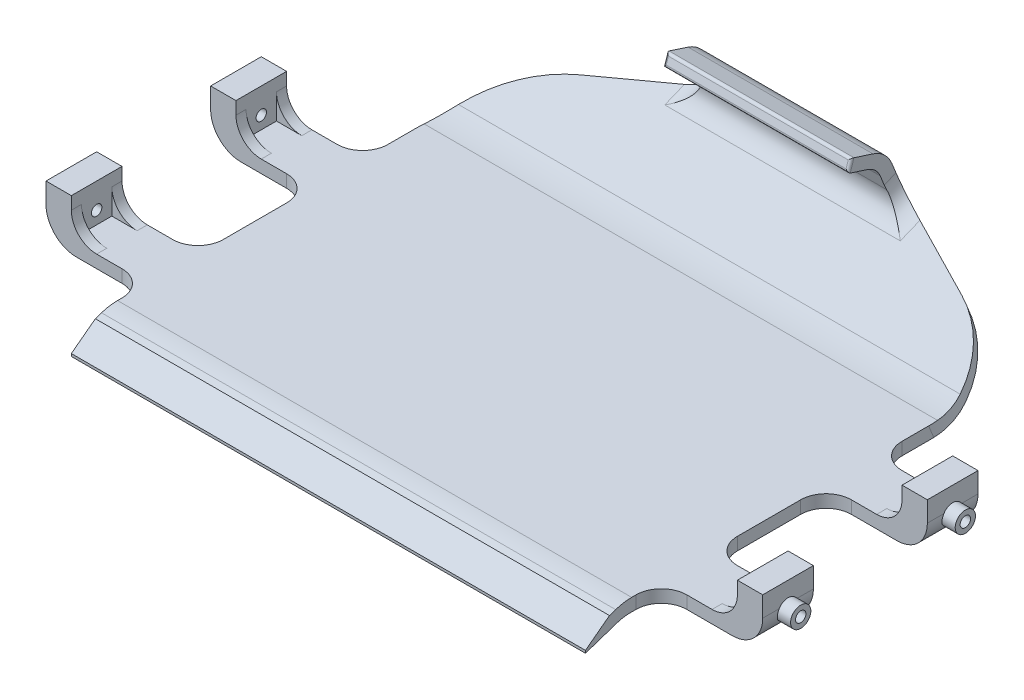
SolidWorks part; units mm, degrees
ref_plane "前视基准面" through (0, 0, 0) normal (0, 0, 1) x (1, 0, 0)
ref_plane "上视基准面" through (0, 0, 0) normal (0, 1, 0) x (1, 0, 0)
ref_plane "右视基准面" through (0, 0, 0) normal (1, 0, 0) x (0, 0, -1)
sketch "Sketch1" plane through (0, 0, 0) normal (0, 1, 0) x (1, 0, 0)
  line L0 (0, 0) -> (203, 0)
  line L1 (203, 0) -> (203, -130)
  line L2 (203, -130) -> (0, -130)
  line L3 (0, -130) -> (0, 0)
  dimension "D1" = 203
  dimension "D2" = 130
extrude "Boss-Extrude1" add sketch "Sketch1" along normal blind 5
sketch "Sketch2" plane through (0, 5, 0) normal (0, 1, 0) x (1, 0, 0)
  line L0 (101.5, 0) -> (101.5, 53.0441) construction
  line L1 (203, 0) -> (0, 0) construction
  line L2 (0, -30) -> (0, -50)
  line L3 (0, 0) -> (0, -130) construction
  line L4 (0, -50) -> (-40, -50)
  line L5 (-40, -50) -> (-40, -30)
  line L6 (-40, -30) -> (0, -30)
  line L7 (0, -95) -> (-40, -95)
  line L8 (-40, -95) -> (-40, -115)
  line L9 (-40, -115) -> (0, -115)
  line L10 (0, -115) -> (0, -95)
  line L11 (243, -115) -> (203, -115)
  line L12 (243, -95) -> (243, -115)
  line L13 (203, -95) -> (243, -95)
  line L14 (203, -115) -> (203, -95)
  line L15 (243, -50) -> (243, -30)
  line L16 (203, -50) -> (243, -50)
  line L17 (203, -30) -> (203, -50)
  line L18 (243, -30) -> (203, -30)
  point P12 (-20, -50)
  point P15 (-20, -115)
  dimension "D1" = 20
  dimension "D2" = 20
  dimension "D3" = 65
  dimension "D4" = 40
  dimension "D5" = 30
  dimension "D6" = 40
extrude "Boss-Extrude2" add sketch "Sketch2" against normal blind 5
sketch "Sketch3" plane through (0, 5, 0) normal (0, 1, 0) x (1, 0, 0)
  line L0 (-40, -30) -> (-40, -50)
  line L1 (-40, -50) -> (-30, -50)
  line L2 (-40, -50) -> (0, -50) construction
  line L3 (-30, -50) -> (-30, -30)
  line L4 (0, -30) -> (-40, -30) construction
  line L5 (-30, -30) -> (-40, -30)
  line L6 (-40, -95) -> (-40, -115)
  line L7 (-40, -115) -> (-30, -115)
  line L8 (-40, -115) -> (0, -115) construction
  line L9 (-30, -115) -> (-30, -95)
  line L10 (0, -95) -> (-40, -95) construction
  line L11 (-30, -95) -> (-40, -95)
  line L12 (101.5, 0) -> (101.5, 18.957) construction
  line L13 (203, 0) -> (0, 0) construction
  line L14 (233, -115) -> (233, -95)
  line L15 (243, -115) -> (233, -115)
  line L16 (243, -95) -> (243, -115)
  line L17 (233, -95) -> (243, -95)
  line L18 (233, -50) -> (233, -30)
  line L19 (243, -50) -> (233, -50)
  line L20 (243, -30) -> (243, -50)
  line L21 (233, -30) -> (243, -30)
  dimension "D1" = 10
  dimension "D2" = 10
extrude "Boss-Extrude3" add sketch "Sketch3" along normal blind 15
sketch "Sketch4" plane through (-40, 0, 0) normal (-1, 0, 0) x (0, 0, 1)
  line L0 (40, 27.3724) -> (40, -12.1388) construction
  line L1 (105, 27.3724) -> (105, -12.1388) construction
  line L2 (25.9041, 10) -> (52.3703, 10) construction
  line L3 (92.0069, 10) -> (116.8425, 10) construction
  line L4 (50, 0) -> (50, 20) construction
  line L5 (115, 0) -> (115, 20) construction
  line L6 (30, 20) -> (50, 20) construction
  circle A0 centre (40, 10) radius 4
  circle A1 centre (105, 10) radius 4
  dimension "D4" = 8
  dimension "D5" = 8
  dimension "D1" = 10
  dimension "D2" = 10
  dimension "D3" = 10
  dimension "D6" = 65
extrude "Boss-Extrude4" add sketch "Sketch4" along normal blind 5
sketch "Sketch6" plane through (243, 0, 0) normal (1, 0, 0) x (0, 0, -1)
  line L0 (-115, 10) -> (-30, 10) construction
  line L1 (-115, 0) -> (-115, 20) construction
  line L2 (-30, 0) -> (-30, 20) construction
  line L3 (-115, 0) -> (-95, 0) construction
  line L4 (-105, 20) -> (-105, 0) construction
  line L5 (-115, 20) -> (-95, 20) construction
  line L6 (-40, 20) -> (-40, 0) construction
  line L7 (-50, 20) -> (-30, 20) construction
  line L8 (-50, 0) -> (-30, 0) construction
  circle A0 centre (-105, 10) radius 4
  circle A1 centre (-40, 10) radius 4
  dimension "D1" = 8
  dimension "D2" = 8
  dimension "D3" = 65
  dimension "D4" = 10
extrude "Boss-Extrude5" add sketch "Sketch6" along normal blind 5
sketch "Sketch5" plane through (-45, 0, 0) normal (-1, 0, 0) x (0, 0, 1)
  circle A0 centre (40, 10) radius 2.05
  circle A1 centre (105, 10) radius 2.05
  dimension "D1" = 4.1
  dimension "D2" = 4.1
extrude "Cut-Extrude1" cut sketch "Sketch5" against normal through all
fillet "Fillet1" radius 10 8 edges at (0, 2.5, 30) (0, 2.5, 95) (0, 2.5, 50) (0, 2.5, 115) (203, 2.5, 115) (203, 2.5, 30) (203, 2.5, 50) (203, 2.5, 95)
fillet "Fillet2" radius 10 4 edges at (-30, 5, 40) (233, 5, 40) (233, 5, 105) (-30, 5, 105)
fillet "Fillet3" radius 12 4 edges at (-40, 0, 105) (-40, 0, 40) (243, 0, 40) (243, 0, 105)
sketch "Sketch10" plane through (0, 0, 0) normal (-1, 0, 0) x (0, 0, 1)
  line L0 (0, 0) -> (-48.0958, 19.432)
  line L1 (-48.0958, 19.432) -> (-46.3592, 23.7303)
  line L2 (-46.3592, 23.7303) -> (0, 5)
  line L3 (0, 5) -> (0, 0)
  line L4 (0, 0) -> (20, 0) construction
  dimension "D1" = 50
  dimension "D2" = 22
extrude "Boss-Extrude8" add sketch "Sketch10" against normal blind 203
fillet "Fillet5" radius 30 1 edges at (101.5, 5, 0)
fillet "Fillet6" radius 45 1 edges at (101.5, 0, 0)
sketch "Sketch11" plane through (0, 4.2983, 1.7366) normal (0, 0.9272, 0.3746) x (1, 0, 0)
  line L0 (101.5, 51.873) -> (101.5, -10.8971) construction
  line L1 (203, 51.873) -> (0, 51.873) construction
  line L2 (0, 21.873) -> (65, 51.873)
  line L3 (0, 7.7044) -> (0, 51.873) construction
  line L4 (65, 51.873) -> (0, 51.873)
  line L5 (0, 51.873) -> (0, 21.873)
  line L6 (138, 51.873) -> (203, 51.873)
  line L7 (203, 21.873) -> (138, 51.873)
  line L8 (203, 51.873) -> (203, 21.873)
  dimension "D1" = 30
  dimension "D2" = 65
extrude "Cut-Extrude3" cut sketch "Sketch11" against normal through all
sketch "Sketch12" plane through (0, 4.2983, 1.7366) normal (0, 0.9272, 0.3746) x (1, 0, 0)
  line L0 (65, 51.873) -> (65, 46.873)
  line L1 (65, 46.873) -> (138, 46.873)
  line L2 (138, 46.873) -> (138, 51.873)
  line L3 (138, 51.873) -> (65, 51.873)
  dimension "D1" = 5
extrude "Boss-Extrude9" add sketch "Sketch12" along normal blind 20
fillet "Fillet7" radius 10 2 edges at (138, 22.7938, -44.0412) (65, 22.7938, -44.0412)
sketch "Sketch13" plane through (65, 0, 0) normal (-1, 0, 0) x (0, 0, 1)
  line L0 (-38.8671, 42.274) -> (-34.2311, 40.401)
  line L1 (-34.2311, 40.401) -> (-34.9804, 38.5466)
  line L2 (-34.9804, 38.5466) -> (-23.6101, 42.241)
  line L3 (-23.6101, 42.241) -> (-25.0767, 46.7548)
  line L4 (-25.0767, 46.7548) -> (-38.8671, 42.274)
  dimension "D1" = 2
  dimension "D2" = 50
  dimension "D3" = 14.5
extrude "Boss-Extrude10" add sketch "Sketch13" against normal blind 73
fillet "Fillet8" radius 8 1 edges at (101.5, 21.8573, -41.7233)
fillet "Fillet9" radius 8 1 edges at (101.5, 38.5466, -34.9804)
fillet "Fillet10" radius 12 1 edges at (101.5, 19.432, -48.0958)
fillet "Fillet11" radius 12 1 edges at (101.5, 42.274, -38.8671)
fillet "Fillet12" radius 1 4 edges at (101.5, 46.7548, -25.0767) (138, 44.4979, -24.3434) (101.5, 42.241, -23.6101) (65, 44.4979, -24.3434)
sketch "Sketch14" plane through (0, 20, 0) normal (0, 1, 0) x (1, 0, 0)
  line L0 (-30, -40) -> (-3.2935, -40) construction
  line L1 (-30, -50) -> (-30, -30) construction
  line L2 (-30, -46) -> (-30, -34)
  line L3 (-30, -34) -> (-10, -34)
  line L4 (-10, -34) -> (-10, -46)
  line L6 (-20, -30) -> (-30, -30) construction
  line L7 (-30, -46) -> (-10, -46)
  line L8 (0, -72.5) -> (17.0763, -72.5) construction
  line L9 (0, -60) -> (0, -85) construction
  line L10 (-30, -111) -> (-10, -111)
  line L11 (-30, -99) -> (-30, -111)
  line L12 (-30, -99) -> (-10, -99)
  line L13 (-10, -111) -> (-10, -99)
  line L14 (101.5, -130) -> (101.5, -95.1913) construction
  line L15 (0, -130) -> (203, -130) construction
  line L16 (233, -99) -> (233, -111)
  line L17 (233, -99) -> (213, -99)
  line L18 (213, -111) -> (213, -99)
  line L19 (233, -111) -> (213, -111)
  line L20 (233, -34) -> (213, -34)
  line L21 (233, -46) -> (233, -34)
  line L22 (233, -46) -> (213, -46)
  line L23 (213, -34) -> (213, -46)
  point P10 (-10, -40)
  dimension "D1" = 4
  dimension "D2" = 20
extrude "Cut-Extrude4" cut sketch "Sketch14" against normal blind 15
fillet "Fillet13" radius 45 2 edges at (0, 10.343, -19.412) (203, 10.343, -19.412)
sketch "Sketch15" plane through (0, 0, 0) normal (-1, 0, 0) x (0, 0, 1)
  line L0 (130, 5) -> (145, 0)
  line L1 (145, 0) -> (145, -5)
  line L2 (145, -5) -> (130, 0)
  line L3 (130, 0) -> (130, 5)
  line L4 (130, 0) -> (156.0185, 0) construction
  point P3 (145.9711, 0)
  dimension "D1" = 15
extrude "Boss-Extrude11" add sketch "Sketch15" against normal blind 203
fillet "Fillet14" radius 20 1 edges at (101.5, 5, 130)
fillet "Fillet15" radius 16 1 edges at (101.5, 0, 130)
sketch "Sketch17" plane through (0, 0, 0) normal (-1, 0, 0) x (0, 0, 1)
  line L0 (145, -4) -> (135.5132, 3.1623)
  line L1 (145, -5) -> (145, 0) construction
  line L2 (145, 0) -> (133.079, 3.9737) construction
  line L3 (135.5132, 3.1623) -> (145, 0)
  line L4 (145, 0) -> (145, -4)
  dimension "D1" = 10
  dimension "D2" = 4
extrude "Cut-Extrude6" cut sketch "Sketch17" against normal blind 203
